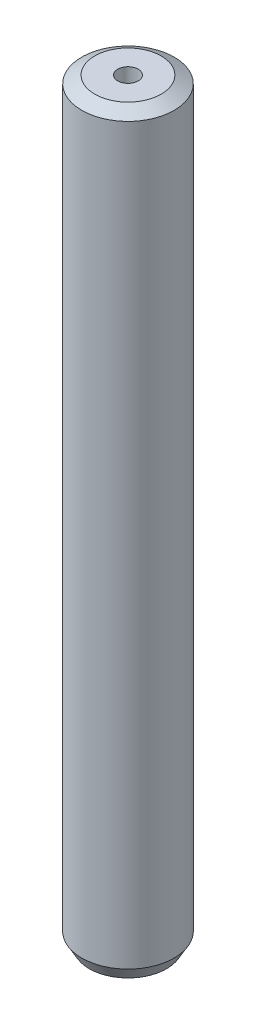
SolidWorks part; units mm, degrees
ref_plane "Front Plane" through (0, 0, 0) normal (0, 0, 1) x (1, 0, 0)
ref_plane "Top Plane" through (0, 0, 0) normal (0, 1, 0) x (1, 0, 0)
ref_plane "Right Plane" through (0, 0, 0) normal (1, 0, 0) x (0, 0, -1)
sketch "Sketch1" plane through (0, 0, 0) normal (0, 1, 0) x (1, 0, 0)
  circle A0 centre (0, 0) radius 7.5
  dimension "SHAFT_OD" = 15
extrude "Boss-Extrude1" add sketch "Sketch1" along normal blind 122.5343
sketch "Sketch2" plane through (0, 0, 0) normal (0, 1, 0) x (1, 0, 0)
  circle A0 centre (0, 0) radius 1.6617
  dimension "BORE_D" = 3.3234
extrude "Cut-Extrude1" cut sketch "Sketch2" along normal through all
chamfer "Chamfer1" distance 1.2194 angle 60 2 edges at (0, 122.5343, 7.5) (0, 0, 7.5) first distance on face at (0, 122.5343, 7.5) first distance on face at (0, 0, 1.6617)
